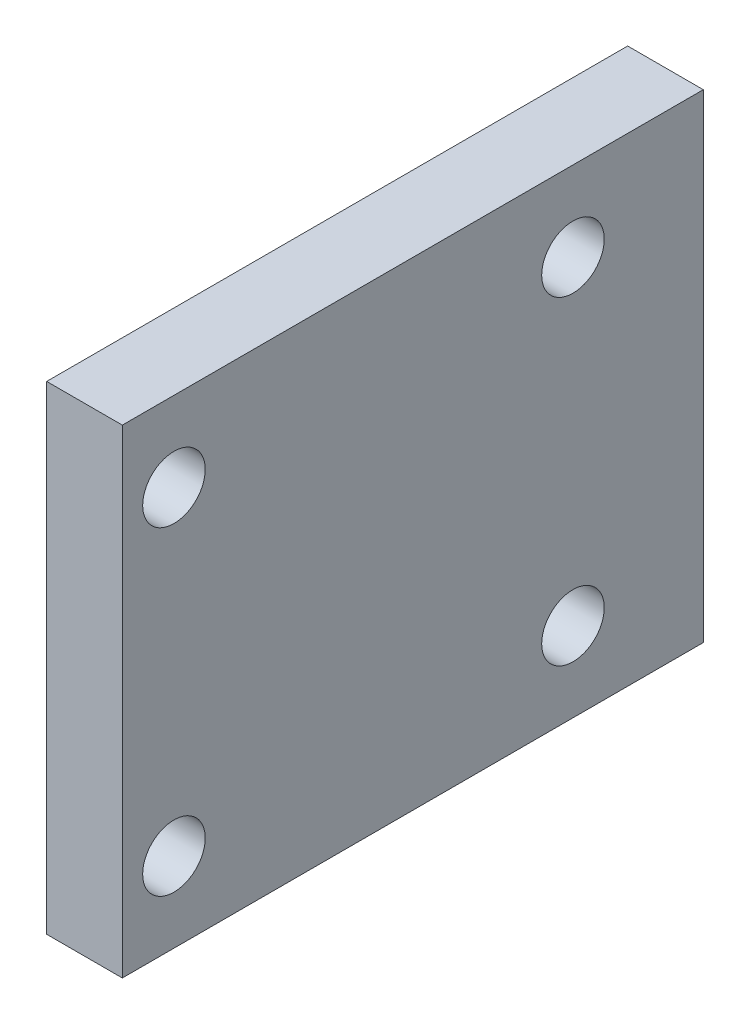
SolidWorks part; units mm, degrees
material "6061 Alloy"
ref_plane "Front Plane" through (0, 0, 0) normal (0, 0, 1) x (1, 0, 0)
ref_plane "Top Plane" through (0, 0, 0) normal (0, 1, 0) x (1, 0, 0)
ref_plane "Right Plane" through (0, 0, 0) normal (1, 0, 0) x (0, 0, -1)
sketch "Sketch2" plane through (-488.9654, 0, 0) normal (1, 0, 0) x (0, 0, -1)
  line L1 (194.9873, 128.4838) -> (194.9873, 166.5838)
  line L2 (194.9873, 126.5338) -> (194.9873, 131.5338) construction
  line L3 (213.8261, 128.4838) -> (140.1661, 128.4838) construction
  line L4 (194.9873, 167.5338) -> (194.9873, 165.7338) construction
  line L5 (140.1661, 166.5838) -> (213.8261, 166.5838) construction
  line L6 (194.9873, 166.5838) -> (148.7593, 166.5838)
  line L7 (148.7593, 166.5838) -> (148.7593, 128.4838)
  line L8 (194.9873, 128.4838) -> (148.7593, 128.4838)
  dimension "D1" = 46.228
extrude "Boss-Extrude1" add sketch "Sketch2" along normal blind 6.0198
hole_wizard "#10 Clearance Hole1" positions "Sketch3" profile "Sketch4" hole size "#10" standard "ANSI Inch"
sketch "Sketch3" plane through (-488.9654, 0, 0) normal (-1, 0, 0) x (0, 0, 1)
  point P0 (-184.6161, 160.2338)
  point P3 (-152.8661, 160.2338)
  point P6 (-152.8661, 134.8338)
  point P9 (-184.6161, 134.8338)
sketch "Sketch4" plane through (-488.9654, 160.2338, -184.6161) normal (0, 1, 0) x (0, 0, 1)
  line L0 (0, 0) -> (0, 26.8957)
  line L1 (0, 26.8957) -> (2.4892, 25.4)
  line L2 (2.4892, 25.4) -> (2.4892, 0)
  line L5 (2.4892, 0) -> (0, 0)
  line L10 (0, 26.8957) -> (-2.4892, 25.4) construction
  line L11 (0, -6.35) -> (0, 107.95) construction
  dimension "Hole Dia." = 4.9784
  dimension "Hole Depth" = 25.4
  dimension "Drill Angle" = 118
